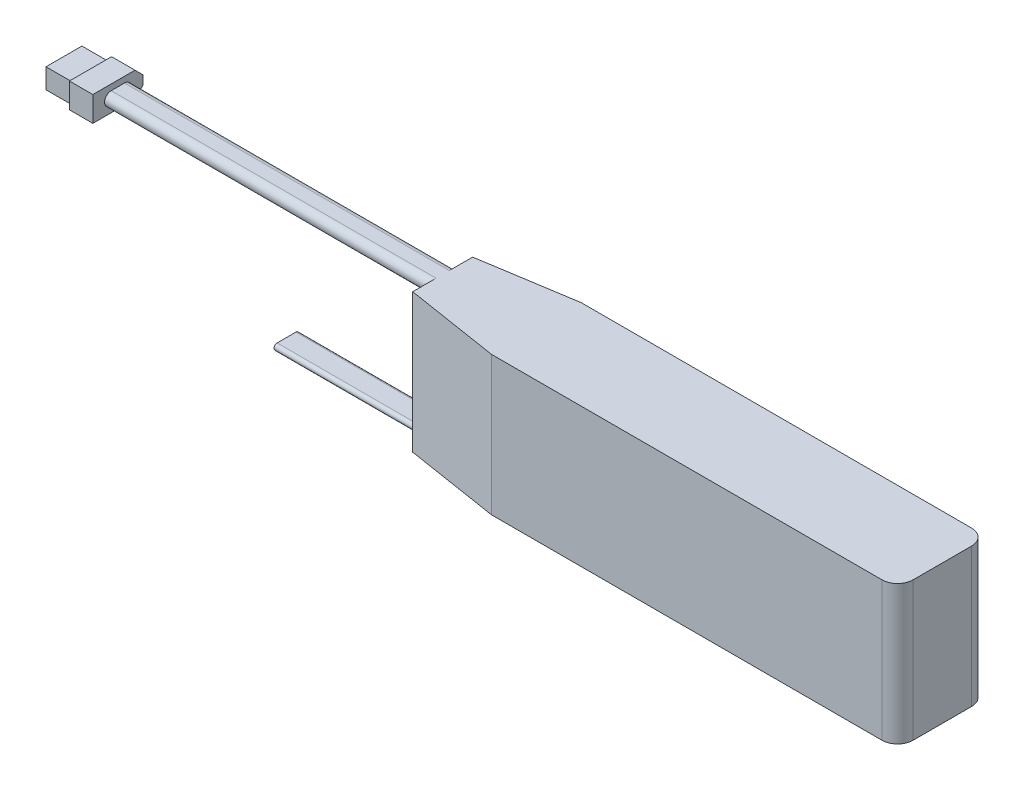
SolidWorks part; units mm, degrees
ref_plane "前基準面" through (0, 0, 0) normal (0, 0, 1) x (1, 0, 0)
ref_plane "上基準面" through (0, 0, 0) normal (0, 1, 0) x (1, 0, 0)
ref_plane "右基準面" through (0, 0, 0) normal (1, 0, 0) x (0, 0, -1)
sketch "草圖1" plane through (0, 0, 0) normal (0, 0, 1) x (1, 0, 0)
  line L1 (0, 0) -> (160, 0)
  line L2 (0, 0) -> (0, 44.5)
  line L3 (0, 44.5) -> (160, 44.5)
  line L4 (160, 0) -> (160, 44.5)
  dimension "D1" = 160
  dimension "D2" = 44.5
extrude "填料-伸長1" add sketch "草圖1" along normal blind 28.7
fillet "圓角1" radius 5 2 edges at (160, 22.25, 0) (160, 22.25, 28.7)
chamfer "導角1" distance 30 angle 9 2 edges at (0, 22.25, 28.7) (0, 22.25, 0) first distance on face at (77.5, 22.25, 28.7) first distance on face at (77.5, 22.25, 0)
ref_plane "平面1" through (0, 0, 0) normal (-1, 0, 0) x (0, 0, 1)
sketch "草圖2" plane through (0, 0, 0) normal (-1, 0, 0) x (0, 0, 1)
  line L1 (23.9485, 0) -> (4.7515, 0) construction
  line L2 (10.35, 2) -> (18.35, 2)
  line L3 (10.35, 2) -> (10.35, 0)
  line L4 (10.35, 0) -> (18.35, 0)
  line L5 (18.35, 2) -> (18.35, 0)
  line L6 (23.9485, 44.5) -> (4.7515, 44.5) construction
  line L7 (10.1, 44.5) -> (18.6, 44.5)
  line L8 (10.1, 44.5) -> (10.1, 40.25)
  line L9 (10.1, 40.25) -> (18.6, 40.25)
  line L10 (18.6, 44.5) -> (18.6, 40.25)
  line L11 (12.225, 42.375) -> (16.475, 42.375) construction
  circle A0 centre (12.225, 42.375) radius 2.125
  circle A1 centre (16.475, 42.375) radius 2.125
  circle A2 centre (11.35, 1) radius 1
  circle A3 centre (13.35, 1) radius 1
  circle A4 centre (15.35, 1) radius 1
  circle A5 centre (17.35, 1) radius 1
  point P19 (14.35, 44.5)
  point P20 (14.35, 44.5)
  point P22 (14.35, 0)
  point P25 (14.35, 0)
  dimension "D1" = 2
  dimension "D2" = 4.25
extrude "填料-伸長6" add sketch "草圖2" along normal blind 120 contours A1 L7 A0 | A1 | A0 | A1 A0 L9 region at (0, 44.0253, 14.35) region at (0, 42.375, 12.225) region at (0, 42.375, 16.475) region at (0, 40.7247, 14.35)
extrude "填料-伸長7" add sketch "草圖2<3>" along normal blind 50 contours A2 | A3 L2 A2 | A3 | A4 L2 A3 | A4 | A5 L2 A4 | A5 | A5 A4 L4 | A4 A3 L4 | A3 A2 L4 region at (0, 1.7766, 12.35) region at (0, 1, 11.35) region at (0, 1.7766, 14.35) region at (0, 1, 13.35) region at (0, 0.2234, 12.35) region at (0, 1.7766, 16.35) region at (0, 1, 15.35) region at (0, 0.2234, 14.35) region at (0, 1, 17.35) region at (0, 0.2234, 16.35)
sketch "草圖2<3>" plane through (0, 0, 0) normal (-1, 0, 0) x (0, 0, 1) same geometry as "草圖2"
ref_plane "平面2" through (-104, 0, 0) normal (-1, 0, 0) x (0, 0, 1)
sketch "草圖3" plane through (-104, 0, 0) normal (-1, 0, 0) x (0, 0, 1)
  line L1 (8.85, 46.375) -> (22.35, 46.375)
  line L2 (6.35, 43.875) -> (6.35, 40.875)
  line L3 (8.85, 38.375) -> (22.35, 38.375)
  line L4 (22.35, 46.375) -> (22.35, 38.375)
  line L5 (7.35, 43.075) -> (9.85, 45.575)
  line L6 (9.85, 45.575) -> (21.35, 45.575)
  line L7 (7.35, 43.075) -> (7.35, 41.675)
  line L8 (9.85, 39.175) -> (14.1167, 39.175)
  line L9 (21.35, 45.575) -> (21.35, 39.175)
  line L10 (7.35, 41.675) -> (9.85, 39.175)
  line L11 (6.35, 43.875) -> (8.85, 46.375)
  line L12 (6.35, 40.875) -> (8.85, 38.375)
  line L13 (16.475, 42.375) -> (3.2966, 42.375) construction
  line L14 (3.2966, 42.375) -> (22.35, 42.375) construction
  line L15 (14.746, 39.175) -> (21.35, 39.175)
  line L17 (14.1167, 39.175) -> (14.1167, 40.4891)
  line L18 (14.1167, 40.4891) -> (14.746, 40.4891)
  line L19 (14.746, 39.175) -> (14.746, 40.4891)
  arc A0 (16.475, 40.25) -> (16.475, 44.5) centre (16.475, 42.375) ccw construction
  arc A1 (12.225, 44.5) -> (12.225, 40.25) centre (12.225, 42.375) ccw construction
  circle A2 centre (16.475, 42.375) radius 1.75
  circle A3 centre (12.225, 42.375) radius 1.75
  point P0 (6.35, 46.375)
  point P2 (6.35, 38.375)
  point P8 (22.35, 42.375)
  point P12 (18.6, 42.375)
  point P13 (7.35, 45.575)
  point P15 (7.35, 39.175)
  point P28 (10.1, 42.375)
  point P29 (7.35, 42.375)
  point P30 (6.35, 42.375)
  dimension "D5" = 3.5
  dimension "D1" = 8
  dimension "D2" = 16
  dimension "D3" = 6.4
  dimension "D4" = 14
extrude "填料-伸長8" add sketch "草圖3" along normal blind 7.5 contours L2 L12 L3 L4 L1 L11 L15 L19 L18 L17 L8 L10 L7 L5 L6 L9 | L19 L15 L9 L6 L5 L7 L10 L8 L17 L18 A3 A2 | A3 | A2 region at (-104, 46.1961, 15.6) region at (-104, 44.2162, 8.7088) region at (-104, 42.375, 16.475) region at (-104, 42.375, 12.225)
extrude "填料-伸長9" add sketch "草圖3<3>" along normal blind 16 contours L19 L15 L9 L6 L5 L7 L10 L8 L17 L18 A3 A2 region at (-104, 44.2162, 8.7088)
sketch "草圖3<3>" plane through (-104, 0, 0) normal (-1, 0, 0) x (0, 0, 1) same geometry as "草圖3"
sketch "草圖4" plane through (-120, 0, 0) normal (-1, 0, 0) x (0, 0, 1)
  line L0 (7.35, 42.375) -> (21.35, 42.375) construction
  line L1 (7.35, 41.675) -> (7.35, 43.075) construction
  line L2 (21.35, 39.175) -> (21.35, 45.575) construction
  circle A0 centre (11.6337, 42.375) radius 1.75
  circle A1 centre (17.1233, 42.375) radius 1.75
  point P10 (0, 0)
  point P11 (17.8007, 42.375)
  point P12 (11.2132, 42.375)
  point P13 (11.6337, 42.375)
  point P14 (17.1233, 42.375)
  dimension "D1" = 3.5
extrude "除料-伸長1" cut sketch "草圖4" against normal blind 8
